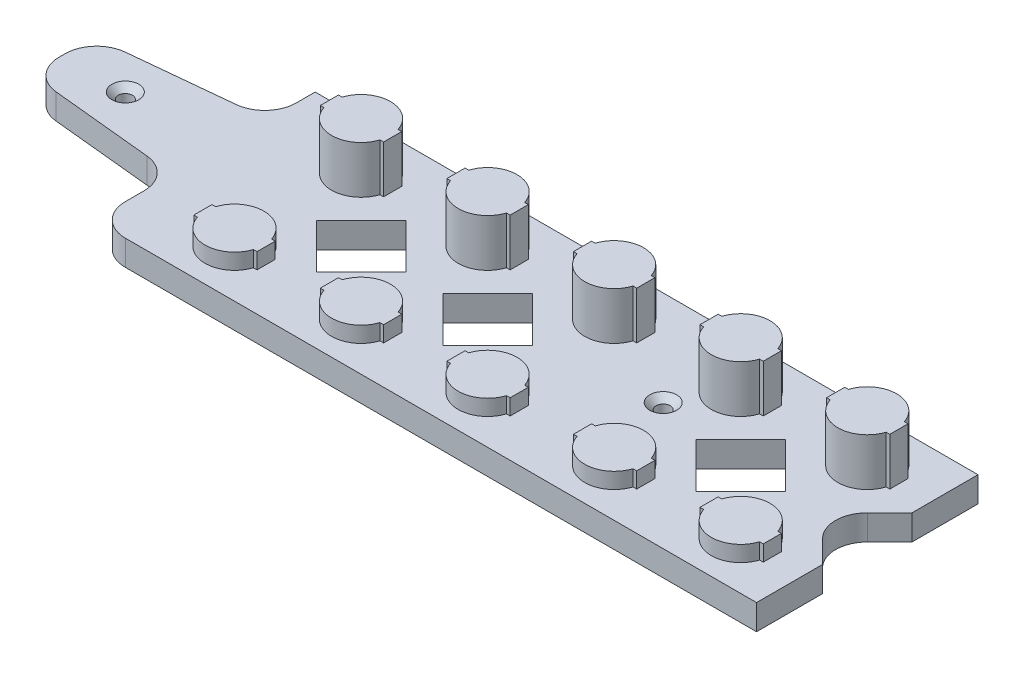
SolidWorks part; units mm, degrees
note: The reader was unsure of these and kept them because the rebuilt part matched: shared geometry of "Sketch3<3>".
ref_plane "Front Plane" through (0, 0, 0) normal (0, 0, 1) x (1, 0, 0)
ref_plane "Top Plane" through (0, 0, 0) normal (0, 1, 0) x (1, 0, 0)
ref_plane "Right Plane" through (0, 0, 0) normal (1, 0, 0) x (0, 0, -1)
sketch "BuildPlate" plane through (0, 0, 0) normal (0, 1, 0) x (1, 0, 0)
  line L0 (0, 0) -> (199.7088, 0) construction
  line L1 (-114.5, -114.5) -> (114.5, -114.5)
  line L2 (-114.5, -114.5) -> (-114.5, 114.5)
  line L3 (-114.5, 114.5) -> (114.5, 114.5)
  line L4 (114.5, -114.5) -> (114.5, 114.5)
  line L5 (-114.5, -114.5) -> (114.5, 114.5) construction
  line L6 (-114.5, 114.5) -> (114.5, -114.5) construction
  circle A0 centre (-85, 85) radius 2.25
  circle A1 centre (85, 85) radius 2.25
  circle A2 centre (85, -85) radius 2.25
  circle A3 centre (-85, -85) radius 2.25
  point P0 (0, 0)
  point P16 (-72.1123, 72.1123)
  dimension "D1" = 170
  dimension "D2" = 229
  dimension "D3" = 4.5
sketch "Sketch1" plane through (0, 0, 0) normal (0, 1, 0) x (1, 0, 0)
  line L1 (-105, 45) -> (154.5, 45)
  line L2 (-105, 45) -> (-105, 115)
  line L3 (-105, 115) -> (154.5, 115)
  line L4 (154.5, 45) -> (154.5, 115)
  line L5 (-105, 45) -> (154.5, 115) construction
  line L6 (-105, 115) -> (154.5, 45) construction
  line L12 (114.5, -114.5) -> (114.5, 114.5) construction
  circle A5 centre (-85, 85) radius 2.25
  circle A6 centre (85, 85) radius 2.25
  dimension "D3" = 4.5
  dimension "D4" = 30
  dimension "D1" = 40
  dimension "D2" = 70
  dimension "D5" = 20
  dimension "D7" = 259.5
extrude "Boss-Extrude1" add sketch "Sketch1" along normal blind 8
sketch "Sketch3" plane through (0, 8, 0) normal (0, 1, 0) x (1, 0, 0)
  line L0 (61.6002, 60) -> (21.2753, 60) construction
  line L1 (-15.5, 100) -> (201.8761, 100) construction
  line L2 (-15.5, 62.875) -> (-16.6555, 62.875)
  line L3 (-15.5, 62.875) -> (-15.5, 57.125)
  line L4 (-15.5, 57.125) -> (-16.6555, 57.125)
  line L5 (-35.5, 62.875) -> (-35.5, 57.125)
  line L6 (-15.5, 62.875) -> (-35.5, 57.125) construction
  line L7 (-15.5, 57.125) -> (-35.5, 62.875) construction
  line L8 (-34.3445, 57.125) -> (-35.5, 57.125)
  line L9 (-34.3445, 62.875) -> (-35.5, 62.875)
  line L10 (24.5, 62.875) -> (23.3445, 62.875)
  line L11 (24.5, 62.875) -> (24.5, 57.125)
  line L12 (24.5, 57.125) -> (23.3445, 57.125)
  line L13 (4.5, 62.875) -> (4.5, 57.125)
  line L14 (5.6555, 57.125) -> (4.5, 57.125)
  line L15 (5.6555, 62.875) -> (4.5, 62.875)
  line L16 (24.5, 62.875) -> (4.5, 57.125) construction
  line L17 (24.5, 57.125) -> (4.5, 62.875) construction
  line L18 (64.5, 62.875) -> (63.3445, 62.875)
  line L19 (64.5, 62.875) -> (64.5, 57.125)
  line L20 (64.5, 57.125) -> (63.3445, 57.125)
  line L21 (44.5, 62.875) -> (44.5, 57.125)
  line L22 (45.6555, 57.125) -> (44.5, 57.125)
  line L23 (45.6555, 62.875) -> (44.5, 62.875)
  line L24 (64.5, 62.875) -> (44.5, 57.125) construction
  line L25 (64.5, 57.125) -> (44.5, 62.875) construction
  line L26 (104.5, 62.875) -> (103.3445, 62.875)
  line L27 (104.5, 62.875) -> (104.5, 57.125)
  line L28 (104.5, 57.125) -> (103.3445, 57.125)
  line L29 (84.5, 62.875) -> (84.5, 57.125)
  line L30 (85.6555, 57.125) -> (84.5, 57.125)
  line L31 (85.6555, 62.875) -> (84.5, 62.875)
  line L32 (104.5, 62.875) -> (84.5, 57.125) construction
  line L33 (104.5, 57.125) -> (84.5, 62.875) construction
  line L34 (144.5, 62.875) -> (143.3445, 62.875)
  line L35 (144.5, 62.875) -> (144.5, 57.125)
  line L36 (144.5, 57.125) -> (143.3445, 57.125)
  line L37 (124.5, 62.875) -> (124.5, 57.125)
  line L38 (125.6555, 57.125) -> (124.5, 57.125)
  line L39 (125.6555, 62.875) -> (124.5, 62.875)
  line L40 (144.5, 62.875) -> (124.5, 57.125) construction
  line L42 (144.5, 57.125) -> (124.5, 62.875) construction
  line L43 (24.5, 102.875) -> (23.3445, 102.875)
  line L44 (24.5, 102.875) -> (24.5, 97.125)
  line L45 (24.5, 97.125) -> (23.3445, 97.125)
  line L46 (4.5, 102.875) -> (4.5, 97.125)
  line L47 (5.6555, 97.125) -> (4.5, 97.125)
  line L48 (5.6555, 102.875) -> (4.5, 102.875)
  line L49 (24.5, 102.875) -> (4.5, 97.125) construction
  line L50 (24.5, 97.125) -> (4.5, 102.875) construction
  line L51 (64.5, 102.875) -> (63.3445, 102.875)
  line L52 (64.5, 102.875) -> (64.5, 97.125)
  line L53 (64.5, 97.125) -> (63.3445, 97.125)
  line L54 (44.5, 102.875) -> (44.5, 97.125)
  line L55 (45.6555, 97.125) -> (44.5, 97.125)
  line L56 (45.6555, 102.875) -> (44.5, 102.875)
  line L57 (64.5, 102.875) -> (44.5, 97.125) construction
  line L58 (64.5, 97.125) -> (44.5, 102.875) construction
  line L59 (104.5, 102.875) -> (103.3445, 102.875)
  line L60 (104.5, 102.875) -> (104.5, 97.125)
  line L61 (104.5, 97.125) -> (103.3445, 97.125)
  line L62 (84.5, 102.875) -> (84.5, 97.125)
  line L63 (85.6555, 97.125) -> (84.5, 97.125)
  line L64 (85.6555, 102.875) -> (84.5, 102.875)
  line L65 (104.5, 102.875) -> (84.5, 97.125) construction
  line L66 (104.5, 97.125) -> (84.5, 102.875) construction
  line L67 (144.5, 102.875) -> (143.3445, 102.875)
  line L68 (144.5, 102.875) -> (144.5, 97.125)
  line L69 (144.5, 97.125) -> (143.3445, 97.125)
  line L70 (124.5, 102.875) -> (124.5, 97.125)
  line L71 (125.6555, 97.125) -> (124.5, 97.125)
  line L72 (125.6555, 102.875) -> (124.5, 102.875)
  line L73 (144.5, 102.875) -> (124.5, 97.125) construction
  line L74 (144.5, 97.125) -> (124.5, 102.875) construction
  line L75 (-15.5, 102.875) -> (-16.6555, 102.875)
  line L76 (-15.5, 102.875) -> (-15.5, 97.125)
  line L77 (-15.5, 97.125) -> (-16.6555, 97.125)
  line L78 (-35.5, 102.875) -> (-35.5, 97.125)
  line L79 (-34.3445, 97.125) -> (-35.5, 97.125)
  line L80 (-34.3445, 102.875) -> (-35.5, 102.875)
  line L81 (-15.5, 102.875) -> (-35.5, 97.125) construction
  line L82 (-15.5, 97.125) -> (-35.5, 102.875) construction
  line L83 (-15.5, 62.875) -> (24.5, 62.875) construction
  line L84 (-15.5, 62.875) -> (-15.5, 102.875) construction
  line L85 (114.5, -114.5) -> (114.5, 114.5) construction
  line L86 (-105, 115) -> (-105, 45) construction
  line L87 (177.0809, 100) -> (177.0809, 60)
  line L88 (177.0809, 80) -> (162.1146, 80) construction
  line L89 (154.5, 45) -> (154.5, 115) construction
  arc A0 (-16.6555, 62.875) -> (-34.4379, 62.5697) centre (-25.5, 60) ccw
  arc A1 (-34.3445, 57.125) -> (-16.6555, 57.125) centre (-25.5, 60) ccw
  arc A2 (23.3445, 62.875) -> (5.5621, 62.5697) centre (14.5, 60) ccw
  arc A3 (5.6555, 57.125) -> (23.3445, 57.125) centre (14.5, 60) ccw
  arc A4 (63.3445, 62.875) -> (45.5621, 62.5697) centre (54.5, 60) ccw
  arc A5 (45.6555, 57.125) -> (63.3445, 57.125) centre (54.5, 60) ccw
  arc A6 (103.3445, 62.875) -> (85.5621, 62.5697) centre (94.5, 60) ccw
  arc A7 (85.6555, 57.125) -> (103.3445, 57.125) centre (94.5, 60) ccw
  arc A8 (143.3445, 62.875) -> (125.5621, 62.5697) centre (134.5, 60) ccw
  arc A9 (125.6555, 57.125) -> (143.3445, 57.125) centre (134.5, 60) ccw
  arc A10 (23.3445, 102.875) -> (5.5621, 102.5697) centre (14.5, 100) ccw
  arc A11 (5.6555, 97.125) -> (23.3445, 97.125) centre (14.5, 100) ccw
  arc A12 (63.3445, 102.875) -> (45.5621, 102.5697) centre (54.5, 100) ccw
  arc A13 (45.6555, 97.125) -> (63.3445, 97.125) centre (54.5, 100) ccw
  arc A14 (103.3445, 102.875) -> (85.5621, 102.5697) centre (94.5, 100) ccw
  arc A15 (85.6555, 97.125) -> (103.3445, 97.125) centre (94.5, 100) ccw
  arc A16 (143.3445, 102.875) -> (125.5621, 102.5697) centre (134.5, 100) ccw
  arc A17 (125.6555, 97.125) -> (143.3445, 97.125) centre (134.5, 100) ccw
  arc A18 (-16.6555, 102.875) -> (-34.4379, 102.5697) centre (-25.5, 100) ccw
  arc A19 (-34.3445, 97.125) -> (-16.6555, 97.125) centre (-25.5, 100) ccw
  point P114 (177.0809, 80)
  point P118 (154.5, 80)
  dimension "D1" = 9.3
  dimension "D2" = 5.75
  dimension "D3" = 10
  dimension "D4" = 5
  dimension "D6" = 40
  dimension "D7" = 40
  dimension "D8" = 20
  dimension "D9" = 69.5
  dimension "D5" = 2
extrude "Boss-Extrude2" add sketch "Sketch3" along normal blind 5
extrude "Boss-Extrude3" add sketch "Sketch3<3>" along normal blind 15
sketch "Sketch3<3>" plane through (0, 8, 0) normal (0, 1, 0) x (1, 0, 0) same geometry as "Sketch3"
chamfer "Chamfer2" distance 2 angle 45 2 edges at (85, 8, -82.75) (-85, 8, -82.75)
sketch "Sketch5" plane through (0, 8, 0) normal (0, 1, 0) x (1, 0, 0)
  line L1 (-105, 115) -> (-105, 45) construction
  line L2 (-105, 75) -> (-55, 70)
  line L3 (-55, 70) -> (-55, 45)
  line L4 (-105, 45) -> (154.5, 45) construction
  line L6 (48.6421, 80) -> (34.5, 94.1421)
  line L8 (48.6421, 80) -> (34.5, 65.8579)
  line L12 (-105, 75) -> (-105, 45)
  line L13 (-105, 45) -> (-55, 45)
  line L21 (-105, 95) -> (-105, 115)
  line L22 (-105, 115) -> (-55, 115)
  line L23 (34.5, 94.1421) -> (20.3579, 80)
  line L24 (34.5, 65.8579) -> (20.3579, 80)
  line L25 (48.6421, 80) -> (20.3579, 80) construction
  line L26 (34.5, 94.1421) -> (34.5, 65.8579) construction
  line L27 (88.6421, 80) -> (74.5, 94.1421) [skipped]
  line L28 (88.6421, 80) -> (74.5, 65.8579) [skipped]
  line L29 (74.5, 94.1421) -> (60.3579, 80) [skipped]
  line L30 (74.5, 65.8579) -> (60.3579, 80) [skipped]
  line L31 (88.6421, 80) -> (60.3579, 80) construction
  line L32 (74.5, 94.1421) -> (74.5, 65.8579) construction
  line L33 (128.6421, 80) -> (114.5, 94.1421)
  line L34 (128.6421, 80) -> (114.5, 65.8579)
  line L35 (114.5, 94.1421) -> (100.3579, 80)
  line L36 (114.5, 65.8579) -> (100.3579, 80)
  line L37 (128.6421, 80) -> (100.3579, 80) construction
  line L38 (114.5, 94.1421) -> (114.5, 65.8579) construction
  line L39 (168.6421, 80) -> (154.5, 94.1421)
  line L40 (168.6421, 80) -> (154.5, 65.8579)
  line L41 (154.5, 94.1421) -> (140.3579, 80)
  line L42 (154.5, 65.8579) -> (140.3579, 80)
  line L43 (168.6421, 80) -> (140.3579, 80) construction
  line L44 (154.5, 94.1421) -> (154.5, 65.8579) construction
  line L45 (-5.5, 80) -> (34.5, 80) construction
  line L71 (154.5, 115) -> (-105, 115) construction
  line L76 (-55, 115) -> (-55, 100)
  line L77 (-55, 100) -> (-105, 95)
  line L82 (-35.5, 57.125) -> (-34.3445, 57.125) construction
  line L83 (-16.6555, 57.125) -> (-15.5, 57.125) construction
  line L88 (-15.5, 57.125) -> (-15.5, 62.875) construction
  line L89 (-15.5, 62.875) -> (-16.6555, 62.875) construction
  line L94 (-34.3445, 62.875) -> (-35.5, 62.875) construction
  line L95 (-35.5, 62.875) -> (-35.5, 57.125) construction
  line L96 (4.5, 97.125) -> (5.6555, 97.125) construction
  line L98 (23.3445, 97.125) -> (24.5, 97.125) construction
  line L99 (24.5, 97.125) -> (24.5, 102.875) construction
  line L100 (24.5, 102.875) -> (23.3445, 102.875) construction
  line L101 (5.6555, 102.875) -> (4.5, 102.875) construction
  line L102 (4.5, 102.875) -> (4.5, 97.125) construction
  line L103 (-35.5, 57.125) -> (-34.3445, 57.125) construction
  line L104 (-16.6555, 57.125) -> (-15.5, 57.125) construction
  line L105 (-15.5, 57.125) -> (-15.5, 62.875) construction
  line L106 (-15.5, 62.875) -> (-16.6555, 62.875) construction
  line L107 (-34.3445, 62.875) -> (-35.5, 62.875) construction
  line L108 (-35.5, 62.875) -> (-35.5, 57.125) construction
  line L109 (4.5, 97.125) -> (5.6555, 97.125) construction
  line L110 (23.3445, 97.125) -> (24.5, 97.125) construction
  line L111 (24.5, 97.125) -> (24.5, 102.875) construction
  line L112 (24.5, 102.875) -> (23.3445, 102.875) construction
  line L113 (5.6555, 102.875) -> (4.5, 102.875) construction
  line L114 (4.5, 102.875) -> (4.5, 97.125) construction
  line L115 (14.5, 100) -> (-25.5, 60) construction
  line L116 (8.6421, 80) -> (-5.5, 94.1421)
  line L117 (8.6421, 80) -> (-5.5, 65.8579)
  line L118 (-5.5, 94.1421) -> (-19.6421, 80)
  line L119 (-5.5, 65.8579) -> (-19.6421, 80)
  line L120 (8.6421, 80) -> (-19.6421, 80) construction
  line L121 (-5.5, 94.1421) -> (-5.5, 65.8579) construction
  arc A19 (-34.3445, 57.125) -> (-16.6555, 57.125) centre (-25.5, 60) ccw construction
  arc A20 (-16.6555, 62.875) -> (-34.3445, 62.875) centre (-25.5, 60) ccw construction
  arc A21 (5.6555, 97.125) -> (23.3445, 97.125) centre (14.5, 100) ccw construction
  arc A22 (23.3445, 102.875) -> (5.6555, 102.875) centre (14.5, 100) ccw construction
  arc A23 (-34.3445, 57.125) -> (-16.6555, 57.125) centre (-25.5, 60) ccw construction
  arc A24 (-16.6555, 62.875) -> (-34.3445, 62.875) centre (-25.5, 60) ccw construction
  arc A25 (5.6555, 97.125) -> (23.3445, 97.125) centre (14.5, 100) ccw construction
  arc A26 (23.3445, 102.875) -> (5.6555, 102.875) centre (14.5, 100) ccw construction
  point P1 (-5.5, 80)
  point P14 (-54.1475, 65.3595)
  point P15 (-5.5, 80)
  point P19 (-53.2791, 100)
  point P23 (34.5, 80)
  point P24 (34.5, 80)
  point P35 (74.5, 80)
  point P46 (74.5, 80)
  point P55 (114.5, 80)
  point P56 (114.5, 80)
  point P61 (154.5, 80)
  point P62 (154.5, 80)
  dimension "D5" = 15
  dimension "D1" = 50
  dimension "D2" = 25
  dimension "D3" = 10
  dimension "D4" = 10
  dimension "D6" = 20
  dimension "D7" = 40
extrude "Cut-Extrude2" cut sketch "Sketch5" against normal through all
fillet "Fillet1" radius 10 6 edges at (-55, 4, -45) (-105, 4, -75) (140.3579, 4, -80) (-55, 4, -70) (-55, 4, -100) (-105, 4, -95)
